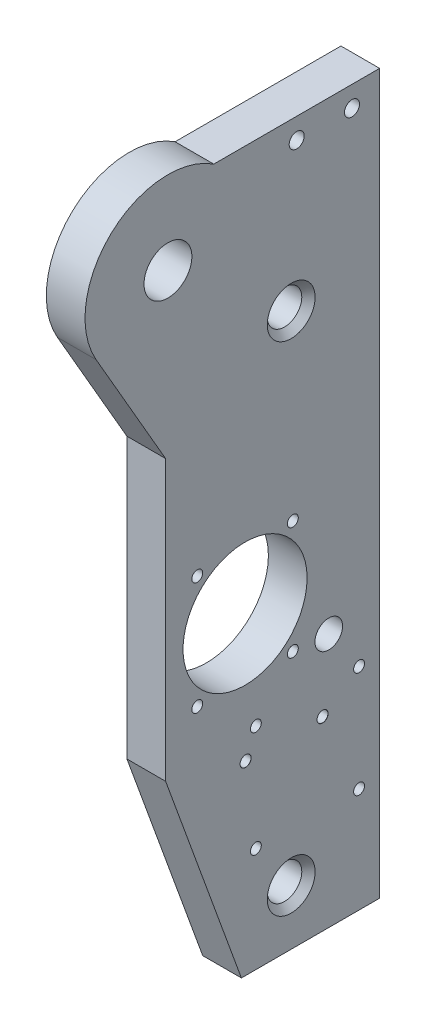
SolidWorks part; units mm, degrees
material "6061-T6 (SS)"
ref_plane "Front Plane" through (0, 0, 0) normal (1, 0, 0) x (0, 1, 0)
ref_plane "Top Plane" through (0, 0, 0) normal (0, 0, 1) x (0, 1, 0)
ref_plane "Right Plane" through (0, 0, 0) normal (0, 1, 0) x (-1, 0, 0)
sketch "Sketch1" plane through (0, 0, 0) normal (1, 0, 0) x (0, 1, 0)
  line L0 (0, 0) -> (-165.1, 0)
  line L1 (-165.1, 0) -> (-165.1, 31.75)
  line L3 (0, 38.1) -> (0, 0)
  line L4 (-117.2613, 49.1619) -> (-53.0543, 49.1619)
  line L5 (-106.0157, 41.8896) -> (-80.055, 41.8896) construction
  line L6 (-106.0157, 41.8896) -> (-106.0157, 19.9342) construction
  line L7 (-106.0157, 19.9342) -> (-80.055, 19.9342) construction
  line L8 (-80.055, 41.8896) -> (-80.055, 19.9342) construction
  line L9 (-106.0157, 41.8896) -> (-80.055, 19.9342) construction
  line L10 (-106.0157, 19.9342) -> (-80.055, 41.8896) construction
  line L12 (-117.2613, 49.1619) -> (-165.1, 31.75)
  line L13 (-25.4, 65.1281) -> (-53.0543, 49.1619)
  line L14 (-4.7625, 6.35) -> (-4.7625, 19.05)
  line L15 (-116.6107, 4.7203) -> (-140.9793, 4.7203) construction
  line L16 (-116.6107, 4.7203) -> (-116.6107, 28.4304) construction
  line L17 (-116.6107, 28.4304) -> (-140.9793, 28.4304) construction
  line L18 (-140.9793, 4.7203) -> (-140.9793, 28.4304) construction
  line L19 (-116.6107, 4.7203) -> (-140.9793, 28.4304) construction
  line L20 (-116.6107, 28.4304) -> (-140.9793, 4.7203) construction
  line L21 (-122.4235, 30.7828) -> (-131.2623, 21.9439) construction
  line L22 (-131.2623, 21.9439) -> (-122.4235, 13.1051) construction
  line L23 (-131.2623, 21.9439) -> (-118.7623, 21.9439) construction
  line L24 (-122.4235, 30.7828) -> (-152.4, 20.32) construction
  circle A1 centre (-152.4, 20.32) radius 3.9687
  circle A2 centre (-38.1, 20.32) radius 3.9687
  circle A3 centre (-93.0353, 30.9119) radius 14.25
  circle A4 centre (-106.6853, 11.684) radius 3.175
  circle A5 centre (-152.4, 20.32) radius 26.035 construction
  circle A6 centre (-38.1, 20.32) radius 26.035 construction
  circle A8 centre (-15.875, 48.6303) radius 50.8 construction
  circle A9 centre (-15.875, 48.6303) radius 19.05
  circle A10 centre (-15.875, 48.6303) radius 5.5
  arc A11 (-122.4235, 30.7828) -> (-122.4235, 13.1051) centre (-131.2623, 21.9439) cw
  point P32 (-118.1369, 19.9342)
  point P33 (-131.2623, 21.9439)
  point P43 (-128.795, 16.5754)
  dimension "D2" = 7.9375
  dimension "D3" = 52.07
  dimension "D5" = 28.5
  dimension "D6" = 6.35
  dimension "D8" = 101.6
  dimension "D11" = 38.1
  dimension "D12" = 11
  dimension "D1" = 165.1
  dimension "D4" = 34
  dimension "D7" = 11.684
  dimension "D9" = 38.1
  dimension "D10" = 38.1
  dimension "D13" = 20.32
  dimension "D14" = 12.7
  dimension "D15" = 15.875
  dimension "D16" = 18.25
  dimension "D17" = 160
  dimension "D18" = 34
  dimension "D19" = 12.7
  dimension "D20" = 4.7625
  dimension "D21" = 6.35
  dimension "D22" = 12.5
  dimension "D23" = 31.75
  dimension "D24" = 150
  dimension "D25" = 31.75
extrude "Boss-Extrude1" add sketch "Sketch1" along normal blind 8.89 contours A9 L13 L4 L12 L1 L0 L3 A4 A3 A2 A1 | A9 A10 region at (0, -81.9252, 21.9882) region at (0, -29.3644, 35.9535)
sketch "Pulley" plane through (0, 0, 0) normal (1, 0, 0) x (0, 1, 0)
  line L0 (-152.7581, 39.8167) -> (-93.219, 40.9102)
  line L1 (-90.7437, 21.178) -> (-107.9659, 17.1233)
  line L2 (-104.0227, 6.7712) -> (-47.3917, 37.464)
  line L3 (-38.1, 0.82) -> (-152.4, 0.82)
  circle A0 centre (-152.4, 20.32) radius 19.5
  circle A1 centre (-38.1, 20.32) radius 19.5
  circle A2 centre (-106.6853, 11.684) radius 5.588
  circle A3 centre (-93.0353, 30.9119) radius 10
  circle A4 centre (-93.0353, 30.9119) radius 14.25 construction
  circle A5 centre (-152.4, 20.32) radius 26.035 construction
  circle A6 centre (-38.1, 20.32) radius 26.035 construction
  circle A7 centre (-15.875, 48.6303) radius 50.8 construction
  dimension "D1" = 20
  dimension "D2" = 39
  dimension "D3" = 39
  dimension "D4" = 11.176
  dimension "D5" = 52.07
  dimension "D6" = 101.6
sketch "Triangle Gaps" plane through (0, 0, 0) normal (1, 0, 0) x (0, 1, 0)
  line L0 (-162.1322, 27.762) -> (-116.4215, 44.3994)
  line L1 (-116.4215, 44.3994) -> (-113.4879, 27.762)
  line L4 (-117.2613, 49.1619) -> (-165.1, 31.75) construction
  line L5 (-117.2613, 49.1619) -> (-116.4215, 44.3994) construction
  line L8 (-165.1, 31.75) -> (-161.9542, 29.5473) construction
  line L9 (-165.1, 0) -> (-165.1, 31.75) construction
  line L10 (-113.4879, 27.762) -> (-162.1322, 27.762)
  line L11 (-71.517, 47.7141) -> (-38.1396, 66.9845)
  line L12 (-38.1396, 66.9845) -> (-45.0981, 47.7141)
  line L13 (-45.0981, 47.7141) -> (-71.517, 47.7141)
  line L14 (-25.4, 65.1281) -> (-53.0543, 49.1619) construction
  line L15 (-82.2692, 37.1381) -> (-76.6428, 19.554)
  line L16 (-76.6428, 19.554) -> (-59.1784, 37.1381)
  line L17 (-59.1784, 37.1381) -> (-82.2692, 37.1381)
  dimension "D1" = 80
  dimension "D2" = 55
  dimension "D3" = 55
  dimension "D4" = 4.7625
hole_wizard "Tap Drill for M3x0.5 Tap1" positions "Sketch5" profile "Sketch6" hole size "M3x0.5" standard "ANSI Metric" end condition up to next
sketch "Sketch5" plane through (8.89, 0, 0) normal (1, 0, 0) x (0, 0, -1)
  point P0 (-41.8896, -80.055)
  point P3 (-19.9342, -80.055)
  point P6 (-19.9342, -106.0157)
  point P9 (-41.8896, -106.0157)
sketch "Sketch6" plane through (8.89, -80.055, 41.8896) normal (0, 1, 0) x (0, 0, -1)
  line L0 (0, 0) -> (0, 8.89)
  line L1 (0, 8.89) -> (1.25, 8.89)
  line L2 (1.25, 8.89) -> (1.25, 0)
  line L5 (1.25, 0) -> (0, 0)
  line L11 (0, -6.35) -> (0, 107.95) construction
  dimension "Thru Hole Dia." = 2.5
  dimension "Thru Hole Depth" = 8.89
hole_wizard "Tap Drill for M3x0.5 Tap2" positions "Sketch7" profile "Sketch8" hole size "M3x0.5" standard "ANSI Metric" end condition up to next
sketch "Sketch7" plane through (8.89, 0, 0) normal (1, 0, 0) x (0, 0, -1)
  point P0 (-4.7203, -116.6107)
  point P3 (-28.4304, -116.6107)
  point P6 (-28.4304, -140.9793)
  point P9 (-4.7203, -140.9793)
sketch "Sketch8" plane through (8.89, -116.6107, 4.7203) normal (0, 1, 0) x (0, 0, -1)
  line L0 (0, 0) -> (0, 8.89)
  line L1 (0, 8.89) -> (1.25, 8.89)
  line L2 (1.25, 8.89) -> (1.25, 0)
  line L5 (1.25, 0) -> (0, 0)
  line L11 (0, -6.35) -> (0, 107.95) construction
  dimension "Thru Hole Dia." = 2.5
  dimension "Thru Hole Depth" = 8.89
hole_wizard "Tap Drill for #8-32 Tap1" positions "Sketch9" profile "Sketch10" hole size "#8-32" standard "ANSI Inch" end condition up to next
sketch "Sketch9" plane through (8.89, 0, 0) normal (1, 0, 0) x (0, 0, -1)
  point P0 (-6.35, -4.7625)
  point P3 (-19.05, -4.7625)
sketch "Sketch10" plane through (8.89, -4.7625, 6.35) normal (0, 1, 0) x (0, 0, -1)
  line L0 (0, 0) -> (0, 8.89)
  line L1 (0, 8.89) -> (1.7272, 8.89)
  line L2 (1.7272, 8.89) -> (1.7272, 0)
  line L5 (1.7272, 0) -> (0, 0)
  line L11 (0, -6.35) -> (0, 107.95) construction
  dimension "Thru Hole Dia." = 3.4544
  dimension "Thru Hole Depth" = 8.89
hole_wizard "Tap Drill for M3x0.5 Tap3" positions "Sketch11" profile "Sketch12" hole size "M3x0.5" standard "ANSI Metric" end condition through all
sketch "Sketch11" plane through (8.89, 0, 0) normal (1, 0, 0) x (0, 0, -1)
  point P0 (-13.1051, -122.4235)
  point P3 (-30.7828, -122.4235)
sketch "Sketch12" plane through (8.89, -122.4235, 13.1051) normal (0, 1, 0) x (0, 0, -1)
  line L0 (0, 0) -> (0, 8.89)
  line L1 (0, 8.89) -> (1.25, 8.89)
  line L2 (1.25, 8.89) -> (1.25, 0.021)
  line L3 (1.25, 0.021) -> (1.275, 0)
  line L5 (1.275, 0) -> (0, 0)
  line L6 (-1.25, 0.021) -> (-1.275, 0) construction
  line L11 (0, -6.35) -> (0, 107.95) construction
  dimension "Thru Hole Dia." = 2.5
  dimension "Thru Hole Depth" = 8.89
  dimension "Near C'Sink Dia." = 2.55
  dimension "Near C'Sink Angle" = 100
chamfer "Chamfer1" distance 1.5316 angle 45 2 edges at (8.89, -38.1, 16.3513) (8.89, -152.4, 16.3513)
equation "\"D4@Sketch1\"=34mm"
equation "\"D5@Sketch1\"=28.5mm"
equation "\"D12@Sketch1\"=11mm"
equation "\"D1@Pulley\" = 20mm"
equation "\"D2@Pulley\"=39mm"
equation "\"D3@Pulley\"=39mm"
equation "\"D16@Sketch1\"=18.25mm"
equation "\"D18@Sketch1\"=34mm"
equation "\"D22@Sketch1\"=12.5mm"
